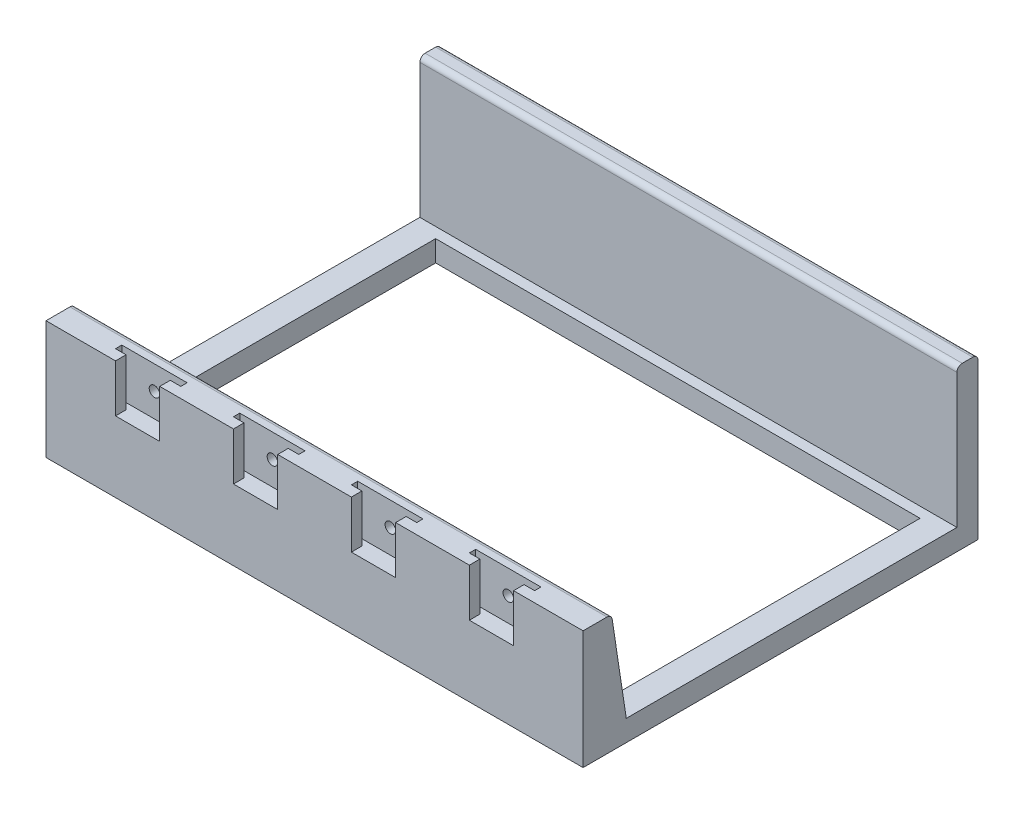
SolidWorks part; units mm, degrees
ref_plane "前视基准面" through (0, 0, 0) normal (0, 0, 1) x (1, 0, 0)
ref_plane "上视基准面" through (0, 0, 0) normal (0, 1, 0) x (1, 0, 0)
ref_plane "右视基准面" through (0, 0, 0) normal (1, 0, 0) x (0, 0, -1)
other "Configuration Table"
sketch "草图1" plane through (0, 0, 0) normal (0, 1, 0) x (1, 0, 0)
  line L1 (0, 0) -> (-102, 0)
  line L2 (0, 0) -> (0, 75)
  line L3 (0, 75) -> (-102, 75)
  line L4 (-102, 0) -> (-102, 75)
  dimension "D1" = 102
  dimension "D2" = 75
extrude "凸台-拉伸1" add sketch "草图1" along normal blind 22.5
sketch "草图2" plane through (0, 22.5, 0) normal (0, 1, 0) x (1, 0, 0)
  line L0 (-102, 75) -> (-102, 0) construction
  line L1 (-90.8, 2) -> (-88.8, 2)
  line L2 (-90.8, 2) -> (-90.8, 3.2)
  line L3 (-90.8, 3.2) -> (-78.4, 3.2)
  line L4 (-78.4, 2) -> (-78.4, 3.2)
  line L5 (-68.4, 2) -> (-66.4, 2)
  line L6 (-68.4, 2) -> (-68.4, 3.2)
  line L7 (-68.4, 3.2) -> (-56, 3.2)
  line L8 (-56, 2) -> (-56, 3.2)
  line L9 (-46, 3.2) -> (-33.6, 3.2)
  line L10 (-46, 3.2) -> (-46, 2)
  line L11 (-46, 2) -> (-44, 2)
  line L12 (-33.6, 3.2) -> (-33.6, 2)
  line L13 (-23.6, 3.2) -> (-11.2, 3.2)
  line L14 (-23.6, 3.2) -> (-23.6, 2)
  line L15 (-23.6, 2) -> (-21.6, 2)
  line L16 (-11.2, 3.2) -> (-11.2, 2)
  line L19 (-102, 0) -> (0, 0) construction
  line L20 (-13.2, 2) -> (-11.2, 2)
  line L22 (-88.8, 2) -> (-88.8, 0)
  line L23 (-88.8, 0) -> (-80.4, 0)
  line L24 (-80.4, 2) -> (-80.4, 0)
  line L26 (-66.4, 2) -> (-66.4, 0)
  line L27 (-66.4, 0) -> (-58, 0)
  line L28 (-58, 2) -> (-58, 0)
  line L30 (-44, 2) -> (-44, 0)
  line L31 (-44, 0) -> (-35.6, 0)
  line L32 (-35.6, 2) -> (-35.6, 0)
  line L34 (-21.6, 2) -> (-21.6, 0)
  line L35 (-21.6, 0) -> (-13.2, 0)
  line L36 (-13.2, 2) -> (-13.2, 0)
  line L37 (-35.6, 2) -> (-33.6, 2)
  line L38 (-58, 2) -> (-56, 2)
  line L39 (-80.4, 2) -> (-78.4, 2)
  point P16 (-68.4, 2.6)
  dimension "D1" = 12.4
  dimension "D2" = 12.4
  dimension "D3" = 12.4
  dimension "D4" = 12.4
  dimension "D5" = 10
  dimension "D6" = 10
  dimension "D7" = 10
  dimension "D8" = 11.2
  dimension "D9" = 2
  dimension "D10" = 2
  dimension "D11" = 2
  dimension "D12" = 2
  dimension "D13" = 1.2
  dimension "D14" = 1.2
  dimension "D15" = 1.2
  dimension "D16" = 1.2
  dimension "D17" = 2
  dimension "D18" = 2
  dimension "D19" = 2
  dimension "D20" = 2
  dimension "D21" = 2
  dimension "D22" = 2
  dimension "D23" = 2
  dimension "D24" = 2
extrude "切除-拉伸1" cut sketch "草图2" against normal offset from surface (9.06 mm away) 13.44 up to face at (-51, 0, -37.5)
sketch "草图3" plane through (0, 22.5, 0) normal (0, 1, 0) x (1, 0, 0)
  line L0 (0, 0) -> (0, 75) construction
  line L1 (-102, 75) -> (0, 75)
  line L2 (-102, 75) -> (-102, 8.2)
  line L3 (-102, 8.2) -> (0, 8.2)
  line L4 (0, 75) -> (0, 8.2)
  line L5 (-11.2, 3.2) -> (-23.6, 3.2) construction
  dimension "D1" = 5
extrude "切除-拉伸2" cut sketch "草图3" against normal blind 12
sketch "草图4" plane through (-102, 0, 0) normal (-1, 0, 0) x (0, 0, 1)
  line L6 (-75, 10.5) -> (-8.2, 10.5) construction
  line L7 (-71, 10.5) -> (-8.2, 10.5)
  line L8 (-71, 10.5) -> (-71, 4)
  line L9 (-71, 4) -> (-8.2, 4)
  line L10 (-8.2, 10.5) -> (-8.2, 4)
  line L11 (-75, 10.5) -> (-75, 0) construction
  line L12 (-75, 0) -> (0, 0) construction
  line L13 (-8.2, 10.5) -> (-8.2, 22.5) construction
  dimension "D1" = 4
  dimension "D2" = 4
extrude "切除-拉伸3" cut sketch "草图4" against normal through all
sketch "草图6" plane through (0, 10.5, 0) normal (0, 1, 0) x (1, 0, 0)
  line L4 (-102, 71) -> (0, 71)
  line L5 (0, 71) -> (0, 75)
  line L6 (0, 75) -> (-102, 75)
  line L7 (-102, 75) -> (-102, 71)
  line L8 (-102, 71) -> (0, 71)
  line L9 (0, 71) -> (0, 75)
  line L10 (0, 75) -> (-102, 75)
  line L11 (-102, 75) -> (-102, 71)
  dimension "D1" = 0
extrude "凸台-拉伸2" add sketch "草图6" along normal blind 20
sketch "草图7" plane through (0, 4, 0) normal (0, 1, 0) x (1, 0, 0)
  line L0 (0, 71) -> (0, 8.2) construction
  line L1 (-97, 69) -> (-5, 69)
  line L2 (-97, 69) -> (-97, 10.2)
  line L3 (-97, 10.2) -> (-5, 10.2)
  line L4 (-5, 69) -> (-5, 10.2)
  line L5 (-102, 71) -> (-102, 8.2) construction
  line L6 (-102, 71) -> (0, 71) construction
  line L7 (0, 8.2) -> (-102, 8.2) construction
  dimension "D1" = 5
  dimension "D2" = 5
  dimension "D3" = 2
  dimension "D4" = 2
extrude "切除-拉伸5" cut sketch "草图7" against normal blind 8
sketch "草图9" plane through (-102, 0, 0) normal (-1, 0, 0) x (0, 0, 1)
  line L0 (-8.2, 22.5) -> (-5.4, 22.5)
  line L2 (-5.4, 22.5) -> (-8.2, 4)
  line L3 (-8.2, 4) -> (-8.2, 22.5)
  dimension "D1" = 2.8
extrude "切除-拉伸6" cut sketch "草图9" against normal blind 108
fillet "圆角2" radius 1 3 edges at (-51, 30.5, -75) (-51, 30.5, -71) (-51, 22.5, -5.4)
sketch "草图10" plane through (0, 0, -3.2) normal (0, 0, 1) x (1, 0, 0)
  line L0 (-88.8, 22.5) -> (-80.4, 13.44) construction
  line L1 (-80.4, 22.5) -> (-88.8, 13.44) construction
  line L2 (-66.4, 22.5) -> (-58, 13.44) construction
  line L3 (-51, 0) -> (-51, 38.7871) construction
  line L4 (-58, 22.5) -> (-66.4, 13.44) construction
  line L5 (-102, 0) -> (0, 0) construction
  circle A0 centre (-84.6, 17.97) radius 1
  circle A1 centre (-62.2, 17.97) radius 1
  circle A2 centre (-39.8, 17.97) radius 1
  circle A3 centre (-17.4, 17.97) radius 1
  dimension "D1" = 2
  dimension "D2" = 2
extrude "切除-拉伸7" cut sketch "草图10" against normal blind 10
